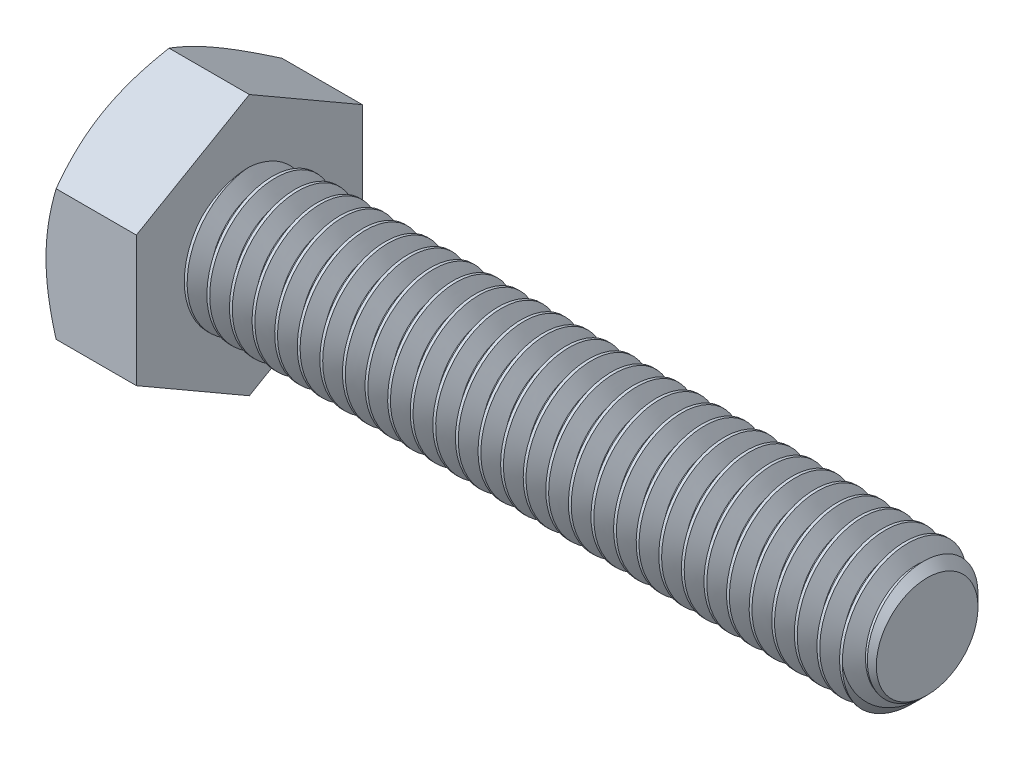
SolidWorks part; units mm, degrees
ref_plane "Front Plane" through (0, 0, 0) normal (0, 0, 1) x (1, 0, 0)
ref_plane "Top Plane" through (0, 0, 0) normal (0, 1, 0) x (1, 0, 0)
ref_plane "Right Plane" through (0, 0, 0) normal (1, 0, 0) x (0, 0, -1)
sketch "Sketch1" plane through (0, 0, 0) normal (0, 0, 1) x (1, 0, 0)
  line L0 (-17, 0) -> (17, 0) construction
  line L1 (-13, 5) -> (-13, -5) construction
  line L2 (-17, 5) -> (-17, -5) construction
  line L3 (17, 3) -> (17, -3) construction
  point P8 (13.5, -3)
  dimension "D1" = 3.5
  dimension "Thread Dia" = 6
  dimension "Hex" = 10
  dimension "Head Ht" = 4
  dimension "Length" = 30
ref_plane "Plane2" through (17, 0, 0) normal (1, 0, 0) x (0, 0, -1)
sketch "Sketch2" plane through (17, 0, 0) normal (1, 0, 0) x (0, 0, -1)
  circle A0 centre (0, 0) radius 3
extrude "Boss-Extrude1" add sketch "Sketch2" against normal up to vertex (30 mm away) up to point (-13, -5, 0)
sketch "Sketch4" plane through (17, 0, 0) normal (1, 0, 0) x (0, 0, -1)
  circle A1 centre (0, 0) radius 3
  circle A2 centre (0, 0) radius 3
  dimension "D1" = 0
curve "Helix/Spiral1" pitch 1 height 31 turns 31 parameters "Pitch"=1
chamfer "Chamfer1" distance 0.75 angle 45 1 edges at (17, 0, -3)
sketch "Sketch5" plane through (0, 0, 0) normal (0, 0, 1) x (1, 0, 0)
  line L0 (17, 3) -> (17.375, 2.3505)
  line L1 (17.375, 2.3505) -> (17.5, 2.3505)
  line L2 (17.5, 2.3505) -> (17.875, 3)
  line L3 (17, 3) -> (17.875, 3)
  line L4 (17.4375, 2.3505) -> (17.4375, 3) construction
  line L5 (17.1875, 2.6752) -> (17.6875, 2.6752) construction
  line L6 (17, -3) -> (17, 3) construction
  dimension "D1" = 60
  dimension "D2" = 0.125
  dimension "D3" = 0.5
sweep "Cut-Sweep1" cut profiles "Sketch5" path "Helix/Spiral1" align with end faces yes
sketch "Sketch3" plane through (-13, 0, 0) normal (-1, 0, 0) x (0, 0, 1)
  line L0 (0, 5) -> (0, -5) construction
  line L1 (-5, -2.8868) -> (0, -5.7735)
  line L2 (0, -5.7735) -> (5, -2.8868)
  line L3 (5, -2.8868) -> (5, 2.8868)
  line L4 (5, 2.8868) -> (0, 5.7735)
  line L5 (0, 5.7735) -> (-5, 2.8868)
  line L6 (-5, 2.8868) -> (-5, -2.8868)
  circle A0 centre (0, 0) radius 5 construction
extrude "Boss-Extrude2" add sketch "Sketch3" along normal up to vertex (4 mm away) up to point (-17, -5, 0)
sketch "Sketch6" plane through (-17, 0, 0) normal (-1, 0, 0) x (0, 0, 1)
  circle A0 centre (0, 0) radius 5 construction
  circle A1 centre (0, 0) radius 5
extrude "Cut-Extrude1" cut sketch "Sketch6" against normal through all draft 60 flip side to cut
sketch "Sketch9" plane through (0, 0, 0) normal (0, 0, 1) x (1, 0, 0)
  line L0 (-13, 3) -> (-13, 0)
  line L1 (-13, 0) -> (-34, 0)
  line L2 (-34, 0) -> (-37, 3)
  line L3 (-37, 3) -> (-13, 3)
  line L4 (-17, 0) -> (17, 0) construction
  line L5 (-13, 5) -> (-13, -5) construction
  line L6 (17, 3) -> (17, -3) construction
  dimension "D1" = 45
  dimension "MinThreadLg" = 54
revolve "Revolve1" [suppressed] add sketch "Sketch9" angle 360 about L1
equation "\"D2@Sketch5\" = \"Pitch@Helix/Spiral1\"*.125"
equation "\"D3@Sketch5\" = \"Pitch@Helix/Spiral1\"*.50"
equation "\"D3@Helix/Spiral1\" = \"Length@Sketch1\"+\"Pitch@Helix/Spiral1\""
equation "\"D1@Chamfer1\" = \"Pitch@Helix/Spiral1\"*.750"
equation "\"D1@Sketch1\" = \"Pitch@Helix/Spiral1\"*3.50"
